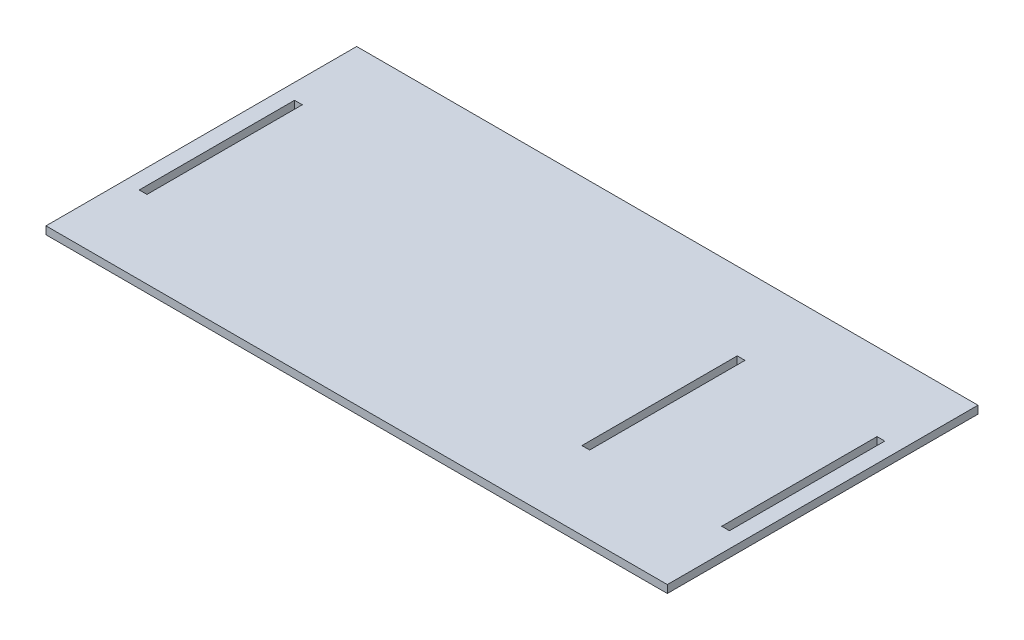
SolidWorks part; units mm, degrees
ref_plane "Alzado" through (0, 0, 0) normal (0, 0, 1) x (1, 0, 0)
ref_plane "Planta" through (0, 0, 0) normal (0, 1, 0) x (1, 0, 0)
ref_plane "Vista lateral" through (0, 0, 0) normal (1, 0, 0) x (0, 0, -1)
sketch "Croquis1" plane through (0, 0, 0) normal (0, 1, 0) x (1, 0, 0)
  line L0 (-200, 0) -> (200, 0) construction
  line L1 (-200, -100) -> (200, -100)
  line L2 (-200, -100) -> (-200, 100)
  line L3 (-200, 100) -> (200, 100)
  line L4 (200, -100) -> (200, 100)
  line L5 (-200, -100) -> (200, 100) construction
  line L6 (-200, 100) -> (200, -100) construction
  line L7 (190, -50) -> (190, 50)
  line L8 (-190, -50) -> (-185, -50)
  line L9 (-190, -50) -> (-190, 50)
  line L10 (-190, 50) -> (-185, 50)
  line L11 (-185, -50) -> (-185, 50)
  line L12 (-190, -50) -> (-185, 50) construction
  line L13 (-190, 50) -> (-185, -50) construction
  line L14 (95, -50) -> (100, -50)
  line L15 (95, -50) -> (95, 50)
  line L16 (95, 50) -> (100, 50)
  line L17 (100, -50) -> (100, 50)
  line L18 (95, -50) -> (100, 50) construction
  line L19 (95, 50) -> (100, -50) construction
  line L20 (185, -50) -> (190, -50)
  line L21 (185, -50) -> (185, 50)
  line L22 (185, 50) -> (190, 50)
  point P0 (0, 0)
  point P8 (-187.5, 0)
  point P13 (97.5, 0)
  dimension "D1" = 200
  dimension "D2" = 400
  dimension "D3" = 100
  dimension "D4" = 10
  dimension "D5" = 5
  dimension "D6" = 5
  dimension "D7" = 100
  dimension "D9" = 10
  dimension "D8" = 2
extrude "Saliente-Extruir1" add sketch "Croquis1" along normal blind 5
